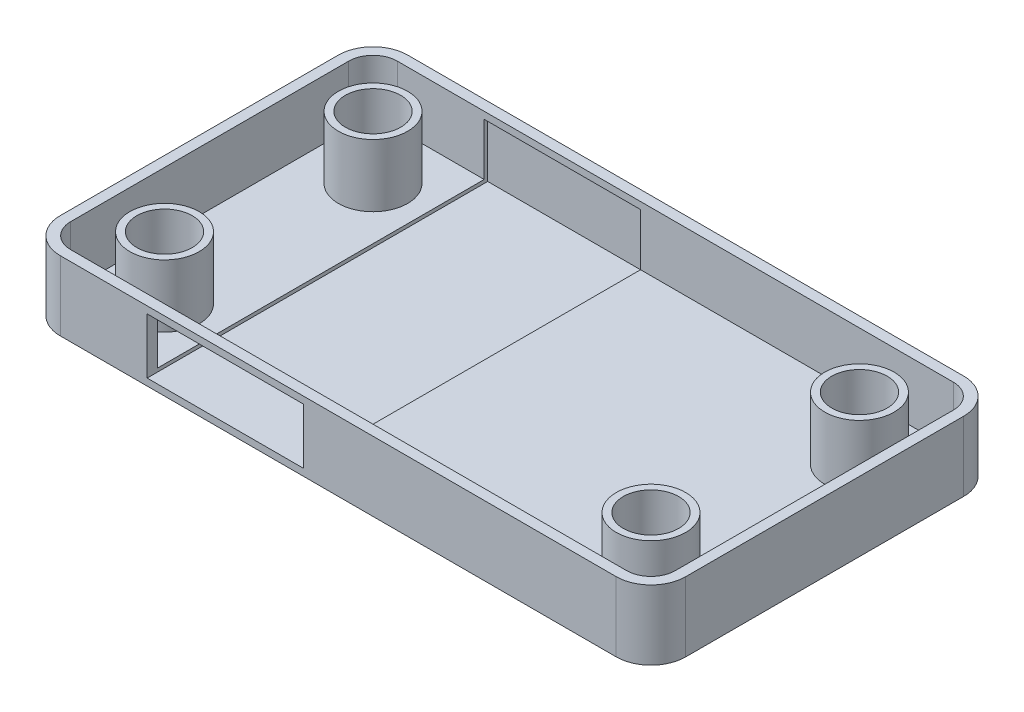
SolidWorks part; units mm, degrees
ref_plane "Front Plane" through (0, 0, 0) normal (0, 0, 1) x (1, 0, 0)
ref_plane "Top Plane" through (0, 0, 0) normal (0, 1, 0) x (1, 0, 0)
ref_plane "Right Plane" through (0, 0, 0) normal (1, 0, 0) x (0, 0, -1)
sketch "Sketch1" plane through (0, 0, 0) normal (0, 1, 0) x (1, 0, 0)
  line L1 (-80, -50) -> (80, -50)
  line L2 (-90, -40) -> (-90, 40)
  line L3 (-80, 50) -> (80, 50)
  line L4 (90, -40) -> (90, 40)
  line L5 (-90, -50) -> (90, 50) construction
  line L6 (-90, 50) -> (90, -50) construction
  arc A0 (-80, -50) -> (-90, -40) centre (-80, -40) cw
  arc A1 (-90, 40) -> (-80, 50) centre (-80, 40) cw
  arc A2 (80, -50) -> (90, -40) centre (80, -40) ccw
  arc A3 (80, 50) -> (90, 40) centre (80, 40) cw
  point P0 (0, 0)
  dimension "D3" = 10
  dimension "D1" = 180
  dimension "D2" = 100
extrude "Boss-Extrude1" add sketch "Sketch1" along normal blind 20 contours L3 A3 L4 A2 L1 A0 L2 A1
shell "Shell1" thickness 3 removed face at (0, 20, 0)
sketch "Sketch3" plane through (0, 3, 0) normal (0, 1, 0) x (1, 0, 0)
  line L0 (-80, 50) -> (80, 50) construction
  line L2 (-90, -40) -> (-90, 40) construction
  line L3 (-90, 0) -> (90, 0) construction
  line L4 (90, -40) -> (90, 40) construction
  line L5 (0, 47) -> (0, -50) construction
  line L6 (-80, 47) -> (80, 47) construction
  line L7 (-80, -50) -> (80, -50) construction
  circle A0 centre (-70, 30) radius 9.9729
  circle A1 centre (-70, 30) radius 7.9729
  circle A2 centre (70, 30) radius 7.9729
  circle A3 centre (70, 30) radius 9.9729
  circle A4 centre (70, -30) radius 7.9729
  circle A5 centre (70, -30) radius 9.9729
  circle A6 centre (-70, -30) radius 7.9729
  circle A7 centre (-70, -30) radius 9.9729
  dimension "D1" = 20
  dimension "D2" = 20
  dimension "D3" = 2
extrude "Boss-Extrude2" add sketch "Sketch3" along normal blind 18
sketch "Sketch4" plane through (0, 0, 50) normal (0, 0, 1) x (1, 0, 0)
  line L0 (-80, 20) -> (80, 20) construction
  line L1 (-55, 18) -> (-10, 18)
  line L2 (-55, 18) -> (-55, 2)
  line L3 (-55, 2) -> (-10, 2)
  line L4 (-10, 18) -> (-10, 2)
  line L5 (-80, 0) -> (80, 0) construction
  line L6 (-90, 20) -> (-90, 0) construction
  line L7 (90, 20) -> (90, 0) construction
  dimension "D1" = 2
  dimension "D2" = 2
  dimension "D3" = 35
  dimension "D4" = 100
extrude "Cut-Extrude2" cut sketch "Sketch4" against normal blind 98
